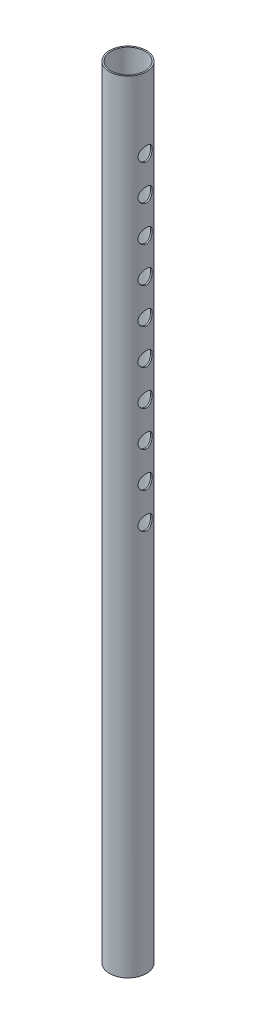
SolidWorks part; units mm, degrees
material "1060 Сплав"
ref_plane "Спереди" through (0, 0, 0) normal (0, 0, 1) x (1, 0, 0)
ref_plane "Сверху" through (0, 0, 0) normal (0, 1, 0) x (1, 0, 0)
ref_plane "Справа" through (0, 0, 0) normal (1, 0, 0) x (0, 0, -1)
sketch "Эскиз1" plane through (0, 0, 0) normal (0, 0, 1) x (1, 0, 0)
  line L0 (0, 0) -> (0, -550)
  dimension "D1" = 550
sketch "Эскиз2" plane through (0, 0, 0) normal (0, 1, 0) x (1, 0, 0)
  circle A0 centre (0, 0) radius 13
  circle A1 centre (0, 0) radius 12
  dimension "D1" = 26
  dimension "D2" = 24
sweep "По траектории1" add profiles "Эскиз2" path "Эскиз1"
sketch "Эскиз3" plane through (0, 0, 0) normal (1, 0, 0) x (0, 0, -1)
  line L0 (0, 0) -> (0, -343.1833) construction
  circle A0 centre (0, -50) radius 5
  circle A1 centre (0, -75) radius 5
  circle A2 centre (0, -100) radius 5
  circle A3 centre (0, -125) radius 5
  circle A4 centre (0, -150) radius 5
  circle A5 centre (0, -175) radius 5
  circle A6 centre (0, -200) radius 5
  circle A7 centre (0, -225) radius 5
  circle A8 centre (0, -250) radius 5
  circle A9 centre (0, -275) radius 5
  dimension "D1" = 10
  dimension "D2" = 25
  dimension "D3" = 25
  dimension "D4" = 25
  dimension "D5" = 25
  dimension "D6" = 25
  dimension "D7" = 25
  dimension "D8" = 25
  dimension "D9" = 25
  dimension "D10" = 50
  dimension "D11" = 25
extrude "Вырез-Вытянуть1" cut sketch "Эскиз3" against normal through all and the other way through all
